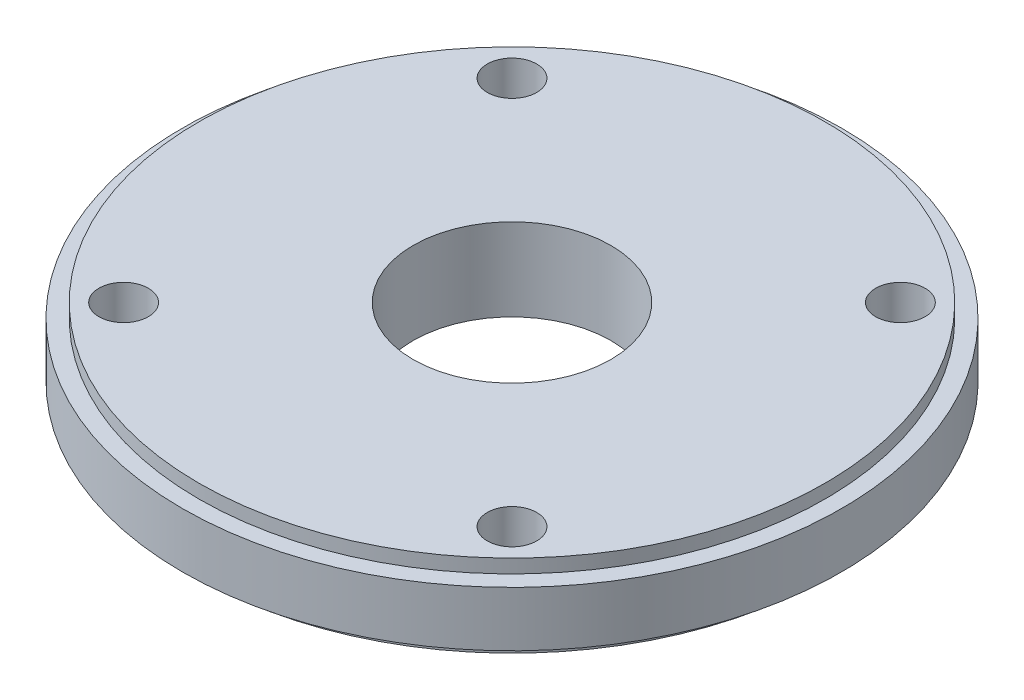
SolidWorks part; units mm, degrees
ref_plane "Front Plane" through (0, 0, 0) normal (0, 0, 1) x (1, 0, 0)
ref_plane "Top Plane" through (0, 0, 0) normal (0, 1, 0) x (1, 0, 0)
ref_plane "Right Plane" through (0, 0, 0) normal (1, 0, 0) x (0, 0, -1)
sketch "Sketch1" plane through (0, 0, 0) normal (0, 1, 0) x (1, 0, 0)
  circle A0 centre (0, 0) radius 57
  circle A1 centre (0, 0) radius 60
  dimension "D1" = 120
  dimension "D2" = 114
extrude "Extrude4" add sketch "Sketch1" along normal mid plane 15 contours A0
extrude "Extrude5" add sketch "Sketch" along normal mid plane 10
sketch "Sketch" plane through (0, 0, 0) normal (0, 1, 0) x (1, 0, 0) same geometry as "Sketch1"
sketch "Sketch5" plane through (0, 0, 0) normal (0, 1, 0) x (1, 0, 0)
  circle A0 centre (0, 0) radius 18
  dimension "D1" = 36
extrude "Extrude6" cut sketch "Sketch5" against normal through all both and the other way through all
ref_axis "Axis1" through (0, -8.25, 0) along (0, 1, 0)
hole_wizard "M8 Clearance Hole2" positions "Sketch21" profile "Sketch22" hole size "M8" standard "ISO" end condition through all
sketch "Sketch21" plane through (0, 7.5, 0) normal (0, 1, 0) x (1, 0, 0)
  line L1 (-707.1068, -707.1068) -> (707.1068, 707.1068) construction
  line L2 (0, -8.25) -> (0, 8.25) construction
  circle A1 centre (15.5563, 15.5563) radius 2.25 construction
  point P0 (-35.3553, -35.3553)
  dimension "D1" = 45
  dimension "D2" = 50
sketch "Sketch22" plane through (-35.3553, 7.5, 35.3553) normal (1, 0, 0) x (0, 0, 1)
  line L0 (0, 0) -> (0, 15)
  line L1 (0, 15) -> (4.5, 15)
  line L2 (4.5, 15) -> (4.5, 0)
  line L5 (4.5, 0) -> (0, 0)
  line L11 (0, -6.35) -> (0, 107.95) construction
  dimension "Thru Hole Dia." = 9
  dimension "Thru Hole Depth" = 15
pattern_circular "CirPattern3" count 4 over 360 about axis through (0, -8.25, 0) along (0, 1, 0) of "M8 Clearance Hole2"
